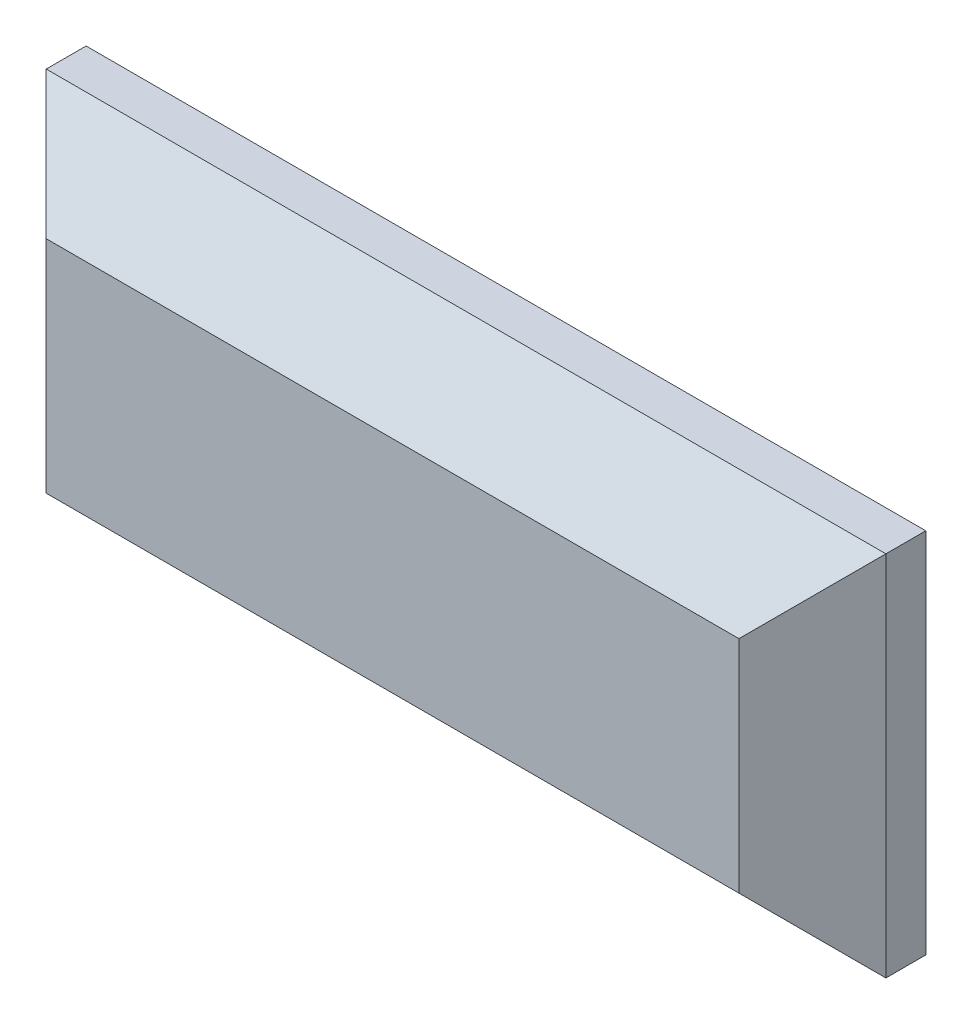
SolidWorks part; units mm, degrees
ref_plane "Спереди" through (0, 0, 0) normal (0, 0, 1) x (1, 0, 0)
ref_plane "Сверху" through (0, 0, 0) normal (0, 1, 0) x (1, 0, 0)
ref_plane "Справа" through (0, 0, 0) normal (1, 0, 0) x (0, 0, -1)
sketch "Эскиз1" plane through (0, 0, 0) normal (0, 0, 1) x (1, 0, 0)
  line L1 (-203.1392, 1392.9521) -> (-123.1392, 1392.9521)
  line L2 (-203.1392, 1392.9521) -> (-203.1392, 1357.9521)
  line L3 (-203.1392, 1357.9521) -> (-123.1392, 1357.9521)
  line L4 (-123.1392, 1392.9521) -> (-123.1392, 1357.9521)
  dimension "D1" = 80
  dimension "D2" = 35
extrude "Бобышка-Вытянуть1" add sketch "Эскиз1" along normal blind 10
sketch "Эскиз7" plane through (0, 0, 0) normal (0, 0, -1) x (-1, 0, 0)
  line L0 (163.1392, 1392.9521) -> (163.1392, 1357.9521) construction
  line L1 (140.6392, 1385.4521) -> (185.6392, 1385.4521)
  line L2 (140.6392, 1385.4521) -> (140.6392, 1365.4521)
  line L3 (140.6392, 1365.4521) -> (185.6392, 1365.4521)
  line L4 (185.6392, 1385.4521) -> (185.6392, 1365.4521)
  line L5 (123.1392, 1392.9521) -> (203.1392, 1392.9521) construction
  line L6 (203.1392, 1357.9521) -> (123.1392, 1357.9521) construction
  line L7 (123.1392, 1375.4521) -> (203.1392, 1375.4521) construction
  line L8 (123.1392, 1357.9521) -> (123.1392, 1392.9521) construction
  line L9 (203.1392, 1392.9521) -> (203.1392, 1357.9521) construction
  point P16 (163.1392, 1385.4521)
  point P17 (140.6392, 1375.4521)
  dimension "D1" = 45
  dimension "D2" = 20
extrude "Бобышка-Вытянуть3" add sketch "Эскиз7" along normal blind 5.5
sketch "Эскиз8" plane through (0, 0, -5.5) normal (0, 0, -1) x (-1, 0, 0)
  line L0 (163.1392, 1385.4521) -> (163.1392, 1365.4521) construction
  line L1 (185.6392, 1385.4521) -> (140.6392, 1385.4521) construction
  line L2 (140.6392, 1365.4521) -> (185.6392, 1365.4521) construction
  line L3 (140.6392, 1375.4521) -> (185.6392, 1375.4521) construction
  line L4 (140.6392, 1385.4521) -> (140.6392, 1365.4521) construction
  line L5 (185.6392, 1365.4521) -> (185.6392, 1385.4521) construction
  circle A0 centre (152.9164, 1375.4521) radius 5.25
  circle A1 centre (173.3621, 1375.4521) radius 5.25
  point P16 (0, 0)
  dimension "D1" = 10.5
  dimension "D2" = 10.5
extrude "Вырез-Вытянуть3" cut sketch "Эскиз8" against normal up to surface (15.5 mm away) up to face at (-163.1392, 1375.4521, 10)
sketch "Эскиз9" plane through (0, 0, 10) normal (0, 0, 1) x (1, 0, 0)
  circle A0 centre (-173.3621, 1375.4521) radius 9
  circle A1 centre (-152.9164, 1375.4521) radius 9
  circle A2 centre (-152.9164, 1375.4521) radius 5.25 construction
  circle A3 centre (-173.3621, 1375.4521) radius 5.25 construction
  dimension "D1" = 18
  dimension "D2" = 18
extrude "Вырез-Вытянуть4" cut sketch "Эскиз9" against normal blind 5
sketch "Эскиз10" plane through (0, 0, 10) normal (0, 0, 1) x (1, 0, 0)
  line L1 (-203.1392, 1392.9521) -> (-123.1392, 1392.9521)
  line L2 (-203.1392, 1392.9521) -> (-203.1392, 1357.9521)
  line L3 (-203.1392, 1357.9521) -> (-123.1392, 1357.9521)
  line L4 (-123.1392, 1392.9521) -> (-123.1392, 1357.9521)
extrude "Бобышка-Вытянуть4" add sketch "Эскиз10" along normal blind 0.8
chamfer "Фаска2" distance 7 angle 45 4 edges at (-163.1392, 1357.9521, 10.8) (-123.1392, 1375.4521, 10.8) (-163.1392, 1392.9521, 10.8) (-203.1392, 1375.4521, 10.8)
ref_plane "Плоскость4" through (-163.1392, 0, 0) normal (-1, 0, 0) x (0, 0, 1)
sketch "Эскиз11" plane through (0, 0, 10) normal (0, 0, -1) x (-1, 0, 0)
  circle A0 centre (152.9164, 1375.4521) radius 0.5
  circle A1 centre (173.3621, 1375.4521) radius 0.5
  circle A2 centre (152.9164, 1375.4521) radius 5.25 construction
  circle A3 centre (173.3621, 1375.4521) radius 5.25 construction
  point P4 (0, 0)
  dimension "D1" = 1
  dimension "D2" = 1
extrude "Бобышка-Вытянуть5" add sketch "Эскиз11" along normal blind 2
fillet "Скругление1" radius 18 2 edges at (-172.8621, 1375.4521, 10) (-152.4164, 1375.4521, 10)
